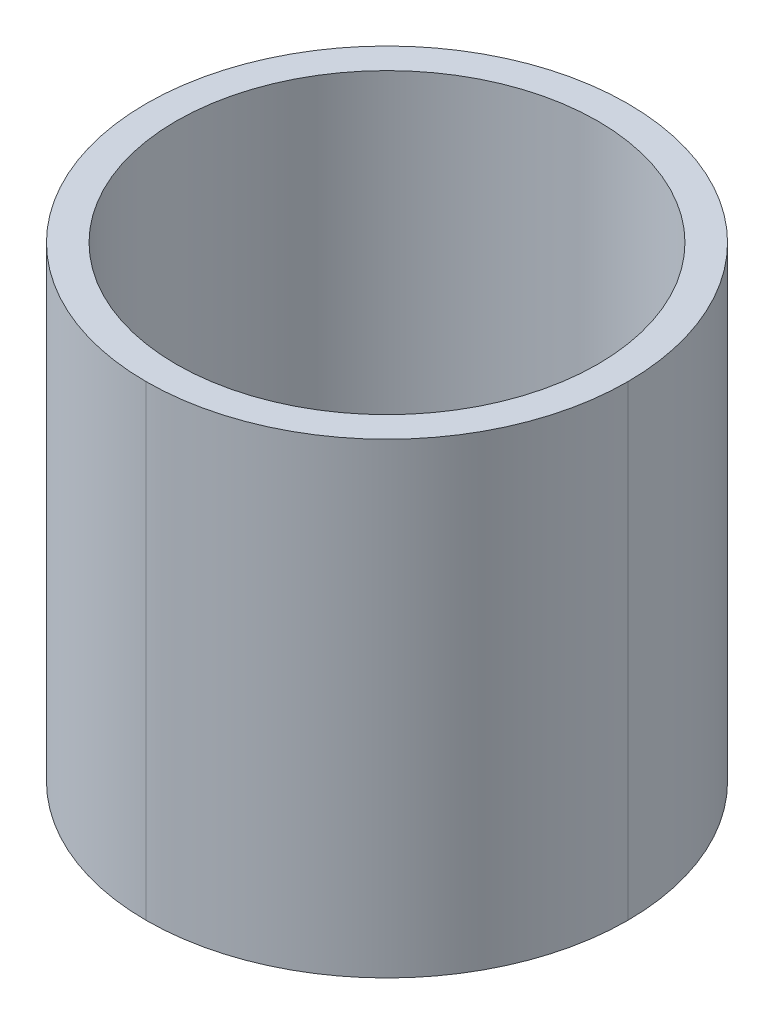
SolidWorks part; units mm, degrees
material "A-Glass Fiber"
ref_plane "Front Plane" through (0, 0, 0) normal (0, 0, 1) x (1, 0, 0)
ref_plane "Top Plane" through (0, 0, 0) normal (0, 1, 0) x (1, 0, 0)
ref_plane "Right Plane" through (0, 0, 0) normal (1, 0, 0) x (0, 0, -1)
sketch "Sketch1" plane through (0, 0, 0) normal (0, 1, 0) x (1, 0, 0)
  line L1 (0, 0) -> (101.6, 0)
  line L2 (0, 0) -> (0, -101.6)
  line L3 (0, -101.6) -> (101.6, -101.6)
  line L4 (101.6, 0) -> (101.6, -101.6)
  dimension "D1" = 101.6
  dimension "D2" = 101.6
extrude "Boss-Extrude1" add sketch "Sketch1" along normal blind 98.425
sketch "Sketch2" plane through (0, 98.425, 0) normal (0, 1, 0) x (1, 0, 0)
  line L0 (0, -101.6) -> (101.6, -101.6) construction
  line L1 (50.8, -101.6) -> (50.8, 0) construction
  line L2 (101.6, 0) -> (0, 0) construction
  line L3 (101.6, -50.8) -> (0, -50.8) construction
  line L4 (101.6, -101.6) -> (101.6, 0) construction
  line L5 (0, 0) -> (0, -101.6) construction
  circle A0 centre (50.8, -50.8) radius 44.45
  point P14 (0, 0)
  point P15 (50.8, -50.8)
  dimension "D1" = 88.9
extrude "Cut-Extrude1" cut sketch "Sketch2" against normal blind 69.85
sketch "Sketch3" plane through (0, 28.575, 0) normal (0, 1, 0) x (1, 0, 0)
  line L0 (6.35, -50.8) -> (95.25, -50.8) construction
  line L1 (28.575, -89.2948) -> (73.025, -12.3052) construction
  line L2 (73.025, -89.2948) -> (28.575, -12.3052) construction
  line L3 (25.1368, -50.8) -> (63.6316, -73.025) construction
  line L4 (25.1368, -50.8) -> (63.6316, -28.575) construction
  line L5 (63.6316, -28.575) -> (63.6316, -73.025) construction
  circle A0 centre (63.6316, -73.025) radius 10.16
  circle A1 centre (50.8, -50.8) radius 44.45 construction
  circle A2 centre (25.1368, -50.8) radius 10.16
  circle A3 centre (63.6316, -28.575) radius 10.16
  circle A4 centre (50.8, -50.8) radius 44.45 construction
  point P11 (50.8, -50.8)
  dimension "D1" = 120
  dimension "D2" = 60
  dimension "D3" = 20.32
  dimension "D4" = 20.32
  dimension "D5" = 20.32
  dimension "D6" = 44.45
extrude "Cut-Extrude2" cut sketch "Sketch3" against normal blind 25.4
fillet "Fillet1" radius 50.8 4 edges at (0, 49.2125, 101.6) (0, 49.2125, 0) (101.6, 49.2125, 0) (101.6, 49.2125, 101.6)
